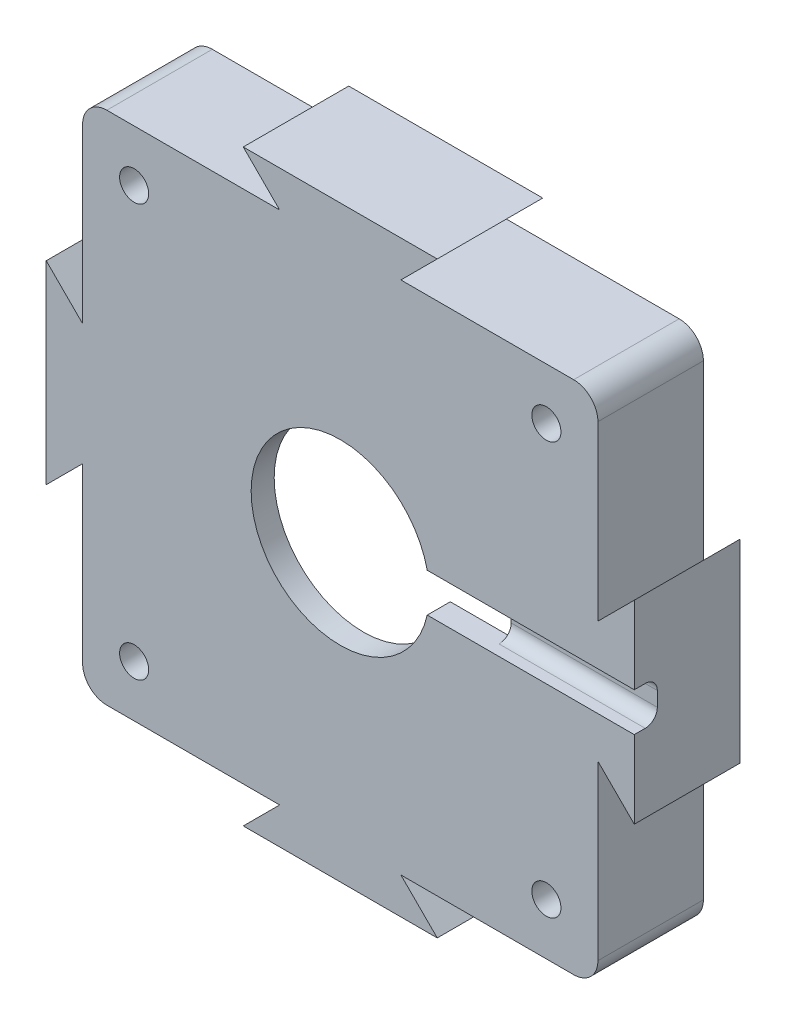
SolidWorks part; units mm, degrees
ref_plane "Front Plane" through (0, 0, 0) normal (0, 0, 1) x (1, 0, 0)
ref_plane "Top Plane" through (0, 0, 0) normal (0, 1, 0) x (1, 0, 0)
ref_plane "Right Plane" through (0, 0, 0) normal (1, 0, 0) x (0, 0, -1)
sketch "Sketch1" plane through (0, 0, 0) normal (0, 0, 1) x (1, 0, 0)
  line L38 (21.25, 5) -> (21.25, 19.25)
  line L39 (19.25, 21.25) -> (5, 21.25)
  line L40 (5, 21.25) -> (8, 24.25)
  line L41 (8, 24.25) -> (-8, 24.25)
  line L42 (-8, 24.25) -> (-5, 21.25)
  line L43 (-5, 21.25) -> (-19.25, 21.25)
  line L44 (-21.25, 19.25) -> (-21.25, 5)
  line L45 (-21.25, 5) -> (-24.25, 8)
  line L46 (-24.25, 8) -> (-24.25, -8)
  line L47 (-24.25, -8) -> (-21.25, -5)
  line L48 (-21.25, -5) -> (-21.25, -19.25)
  line L49 (-19.25, -21.25) -> (-5, -21.25)
  line L50 (-5, -21.25) -> (-8, -24.25)
  line L51 (-8, -24.25) -> (8, -24.25)
  line L52 (8, -24.25) -> (5, -21.25)
  line L53 (5, -21.25) -> (19.25, -21.25)
  line L54 (21.25, -19.25) -> (21.25, -5)
  line L55 (21.25, -5) -> (24.25, -8)
  line L56 (24.25, -8) -> (24.25, 8)
  line L57 (24.25, 8) -> (21.25, 5)
  line L58 (21.25, 5) -> (21.25, 19.25)
  line L59 (19.25, 21.25) -> (5, 21.25)
  line L60 (5, 21.25) -> (8, 24.25)
  line L61 (8, 24.25) -> (-8, 24.25)
  line L62 (-8, 24.25) -> (-5, 21.25)
  line L63 (-5, 21.25) -> (-19.25, 21.25)
  line L64 (-21.25, 19.25) -> (-21.25, 5)
  line L65 (-21.25, 5) -> (-24.25, 8)
  line L66 (-24.25, 8) -> (-24.25, -8)
  line L67 (-24.25, -8) -> (-21.25, -5)
  line L68 (-21.25, -5) -> (-21.25, -19.25)
  line L69 (-19.25, -21.25) -> (-5, -21.25)
  line L70 (-5, -21.25) -> (-8, -24.25)
  line L71 (-8, -24.25) -> (8, -24.25)
  line L72 (8, -24.25) -> (5, -21.25)
  line L73 (5, -21.25) -> (19.25, -21.25)
  line L74 (21.25, -19.25) -> (21.25, -5)
  line L75 (21.25, -5) -> (24.25, -8)
  line L76 (24.25, -8) -> (24.25, 8)
  line L77 (24.25, 8) -> (21.25, 5)
  circle A8 centre (-17, -17) radius 1.2 construction
  circle A9 centre (17, -17) radius 1.2 construction
  circle A10 centre (17, 17) radius 1.2 construction
  circle A11 centre (-17, 17) radius 1.2 construction
  circle A12 centre (-17, -17) radius 1.2
  circle A13 centre (17, -17) radius 1.2
  circle A14 centre (17, 17) radius 1.2
  circle A15 centre (-17, 17) radius 1.2
  arc A22 (21.25, 19.25) -> (19.25, 21.25) centre (19.25, 19.25) ccw
  arc A23 (-19.25, 21.25) -> (-21.25, 19.25) centre (-19.25, 19.25) ccw
  arc A24 (-21.25, -19.25) -> (-19.25, -21.25) centre (-19.25, -19.25) ccw
  arc A25 (19.25, -21.25) -> (21.25, -19.25) centre (19.25, -19.25) ccw
  arc A26 (21.25, 19.25) -> (19.25, 21.25) centre (19.25, 19.25) ccw
  arc A27 (-19.25, 21.25) -> (-21.25, 19.25) centre (-19.25, 19.25) ccw
  arc A28 (-21.25, -19.25) -> (-19.25, -21.25) centre (-19.25, -19.25) ccw
  arc A29 (19.25, -21.25) -> (21.25, -19.25) centre (19.25, -19.25) ccw
  dimension "D1" = 0
extrude "Boss-Extrude1" add sketch "Sketch1" along normal offset from surface (8.7 mm away) 2 offset beyond the face yes
sketch "Sketch2" plane through (0, 0, 0) normal (0, 0, -1) x (-1, 0, 0)
  line L0 (19.25, -19.25) -> (-19.25, -19.25) construction
  line L2 (-19.25, 19.25) -> (19.25, 19.25) construction
  line L3 (19.25, 19.25) -> (19.25, -19.25) construction
  line L4 (17, 14.55) -> (19.25, 14.55) construction
  line L5 (14.55, 19.25) -> (14.55, 17) construction
  line L6 (-14.55, 17) -> (-14.55, 19.25) construction
  line L7 (-19.25, 14.55) -> (-17, 14.55) construction
  line L8 (-14.55, -19.25) -> (-14.55, -17) construction
  line L9 (-17, -14.55) -> (-19.25, -14.55) construction
  line L10 (19.25, -14.55) -> (17, -14.55) construction
  line L11 (14.55, -17) -> (14.55, -19.25) construction
  line L12 (14.55, -19.25) -> (-14.55, -19.25)
  line L13 (-19.25, -14.55) -> (-19.25, 14.55)
  line L14 (-14.55, 19.25) -> (14.55, 19.25)
  line L15 (19.25, 14.55) -> (19.25, -14.55)
  line L16 (17, 14.55) -> (19.25, 14.55)
  line L17 (14.55, 19.25) -> (14.55, 17)
  line L18 (-14.55, 17) -> (-14.55, 19.25)
  line L19 (-19.25, 14.55) -> (-17, 14.55)
  line L20 (-14.55, -19.25) -> (-14.55, -17)
  line L21 (-17, -14.55) -> (-19.25, -14.55)
  line L22 (19.25, -14.55) -> (17, -14.55)
  line L23 (14.55, -17) -> (14.55, -19.25)
  arc A0 (14.55, 17) -> (17, 14.55) centre (17, 17) ccw construction
  arc A1 (-17, 14.55) -> (-14.55, 17) centre (-17, 17) ccw construction
  arc A2 (-14.55, -17) -> (-17, -14.55) centre (-17, -17) ccw construction
  arc A3 (17, -14.55) -> (14.55, -17) centre (17, -17) ccw construction
  arc A4 (14.55, 17) -> (17, 14.55) centre (17, 17) ccw
  arc A5 (-17, 14.55) -> (-14.55, 17) centre (-17, 17) ccw
  arc A6 (-14.55, -17) -> (-17, -14.55) centre (-17, -17) ccw
  arc A7 (17, -14.55) -> (14.55, -17) centre (17, -17) ccw
extrude "Cut-Extrude2" cut sketch "Sketch2" against normal blind 3
sketch "Sketch3" plane through (0, 0, 3) normal (0, 0, -1) x (-1, 0, 0)
  line L0 (-12, -6) -> (-12, 6) construction
  line L1 (5, -13) -> (-5, -13) construction
  line L2 (12, 6) -> (12, -6) construction
  line L3 (-5, 13) -> (5, 13) construction
  line L4 (-12, -6) -> (-12, 6) construction
  line L5 (5, -13) -> (-5, -13) construction
  line L6 (12, 6) -> (12, -6) construction
  line L7 (-5, 13) -> (5, 13) construction
  line L8 (-12.2, -6) -> (-12.2, 6)
  line L9 (-5, 13.2) -> (5, 13.2)
  line L10 (12.2, 6) -> (12.2, -6)
  line L11 (5, -13.2) -> (-5, -13.2)
  arc A0 (-5, 13) -> (-12, 6) centre (-5, 6) ccw construction
  arc A1 (-12, -6) -> (-5, -13) centre (-5, -6) ccw construction
  arc A2 (5, -13) -> (12, -6) centre (5, -6) ccw construction
  arc A3 (12, 6) -> (5, 13) centre (5, 6) ccw construction
  arc A4 (-5, 13) -> (-12, 6) centre (-5, 6) ccw construction
  arc A5 (-12, -6) -> (-5, -13) centre (-5, -6) ccw construction
  arc A6 (5, -13) -> (12, -6) centre (5, -6) ccw construction
  arc A7 (12, 6) -> (5, 13) centre (5, 6) ccw construction
  arc A8 (-5, 13.2) -> (-12.2, 6) centre (-5, 6) ccw
  arc A9 (12.2, 6) -> (5, 13.2) centre (5, 6) ccw
  arc A10 (5, -13.2) -> (12.2, -6) centre (5, -6) ccw
  arc A11 (-12.2, -6) -> (-5, -13.2) centre (-5, -6) ccw
  dimension "D1" = 0.2
extrude "Cut-Extrude3" cut sketch "Sketch3" against normal blind 3.8
sketch "Sketch4" plane through (0, 0, 8.7) normal (0, 0, 1) x (1, 0, 0)
  line L3 (7.0308, -1.3) -> (7.95, -1.3)
  line L4 (7.95, -1.3) -> (7.95, 1.3)
  line L5 (7.95, 1.3) -> (7.0308, 1.3)
  line L9 (7.95, -1.3) -> (7.95, 1.3) construction
  line L10 (8.15, -1.5) -> (8.15, 1.5) construction
  line L11 (8.15, 1.5) -> (7.1953, 1.5) construction
  line L12 (7.95, 1.3) -> (7.0308, 1.3) construction
  line L13 (7.0308, -1.3) -> (7.95, -1.3) construction
  line L14 (7.1953, -1.5) -> (8.15, -1.5) construction
  line L16 (24.25, 1.6) -> (7.1737, 1.6)
  line L17 (24.25, 1.6) -> (24.25, -1.6)
  line L18 (24.25, -1.6) -> (7.1737, -1.6)
  line L20 (24.25, 8) -> (24.25, -8) construction
  line L21 (24.25, 0) -> (0, 0) construction
  arc A0 (7.1737, 1.6) -> (7.1737, -1.6) centre (0, 0) ccw
  arc A1 (7.0308, 1.3) -> (7.0308, -1.3) centre (0, 0) ccw
  arc A2 (7.0308, 1.3) -> (7.0308, -1.3) centre (0, 0) ccw construction
  arc A3 (7.1953, 1.5) -> (7.1953, -1.5) centre (0, 0) ccw construction
  point P11 (24.25, -1.6)
  dimension "D3" = 3.2
  dimension "D1" = 0
  dimension "D2" = 0.2
extrude "Cut-Extrude4" cut sketch "Sketch4" against normal up to surface (1.9 mm away) up to face at (0, 0, 6.8)
sketch "Sketch5" plane through (0, 0, 0) normal (0, 0, -1) x (-1, 0, 0)
  line L1 (-19.25, -11.05) -> (-20.25, -11.05)
  line L2 (-19.25, -11.05) -> (-19.25, -9.55)
  line L3 (-19.25, -9.55) -> (-20.25, -9.55)
  line L4 (-20.25, -11.05) -> (-20.25, -9.55)
  line L5 (-19.75, -9.55) -> (-19.75, -11.05) construction
  line L6 (-19.25, -10.3) -> (-20.25, -10.3) construction
  line L7 (-19.25, 14.55) -> (-19.25, -14.55) construction
  point P4 (-19.25, -9.55)
  point P356 (-19.75, -10.3)
  dimension "D1" = 8
  dimension "D2" = 1.5
  dimension "D3" = 1
extrude "Cut-Extrude5" cut sketch "Sketch5" against normal up to surface (3 mm away) up to face at (0, 0, 3)
fillet "Fillet1" radius 1 4 edges at (19.25, -11.05, 1.5) (19.25, -9.55, 1.5) (18.225, -1.6, 6.8) (18.225, 1.6, 6.8)
